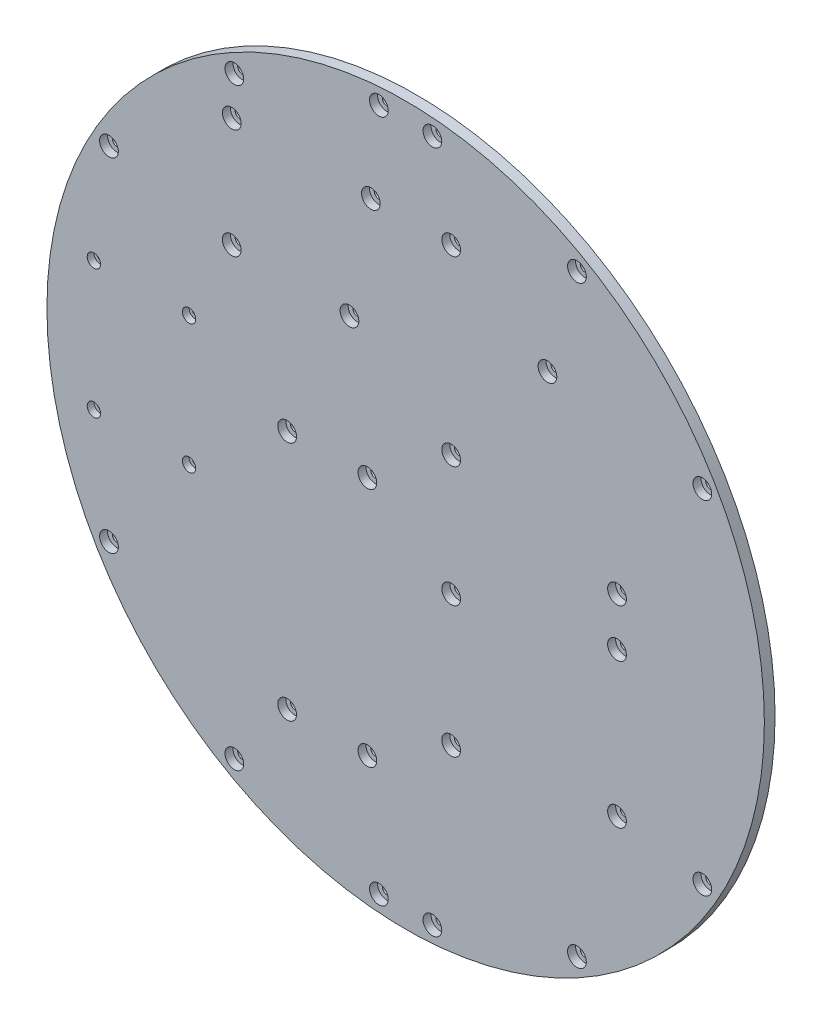
SolidWorks part; units mm, degrees
ref_plane "Plan de face" through (0, 0, 0) normal (0, 0, 1) x (1, 0, 0)
ref_plane "Plan de dessus" through (0, 0, 0) normal (0, 1, 0) x (1, 0, 0)
ref_plane "Plan de droite" through (0, 0, 0) normal (1, 0, 0) x (0, 0, -1)
sketch "Esquisse1" plane through (0, 0, 0) normal (0, 0, 1) x (1, 0, 0)
  line L0 (0, 0) -> (0, -128.06) construction
  line L1 (10, -127.669) -> (-10, -127.669) construction
  line L2 (0, 0) -> (0, 128.06) construction
  line L3 (10, 127.669) -> (-10, 127.669) construction
  line L4 (-64.03, -110.9032) -> (64.03, 110.9032) construction
  line L5 (110.9032, 64.03) -> (-110.9032, -64.03) construction
  line L6 (-64.03, 110.9032) -> (64.03, -110.9032) construction
  line L7 (-110.9032, 64.03) -> (110.9032, -64.03) construction
  circle A0 centre (0, 0) radius 134.09
  circle A1 centre (10, -127.669) radius 1.75
  circle A2 centre (-10, -127.669) radius 1.75
  circle A3 centre (0, 0) radius 128.06 construction
  circle A4 centre (10, 127.669) radius 1.75
  circle A5 centre (-10, 127.669) radius 1.75
  circle A6 centre (64.03, 110.9032) radius 1.75
  circle A7 centre (110.9032, 64.03) radius 1.75
  circle A8 centre (110.9032, -64.03) radius 1.75
  circle A9 centre (64.03, -110.9032) radius 1.75
  circle A10 centre (-64.03, -110.9032) radius 1.75
  circle A11 centre (-110.9032, -64.03) radius 1.75
  circle A12 centre (-110.9032, 64.03) radius 1.75
  circle A13 centre (-64.03, 110.9032) radius 1.75
  point P7 (0, -127.669)
  point P14 (0, 127.669)
  point P17 (0, 0)
  point P18 (0, 0)
  point P23 (0, 0)
  point P26 (0, 0)
  dimension "D1" = 256.12
  dimension "D3" = 3.5
  dimension "D8" = 268.18
  dimension "D2" = 20
  dimension "D4" = 30
  dimension "D5" = 30
  dimension "D6" = 30
  dimension "D7" = 30
extrude "Boss.-Extru.1" add sketch "Esquisse1" along normal blind 4
sketch "Esquisse2" plane through (0, 0, 4) normal (0, 0, 1) x (1, 0, 0)
  circle A0 centre (64.03, -110.9032) radius 3.5
  circle A1 centre (110.9032, -64.03) radius 3.5
  circle A2 centre (110.9032, 64.03) radius 3.5
  circle A3 centre (64.03, 110.9032) radius 3.5
  circle A4 centre (10, 127.669) radius 3.5
  circle A5 centre (-10, 127.669) radius 3.5
  circle A6 centre (-64.03, 110.9032) radius 3.5
  circle A7 centre (-110.9032, 64.03) radius 3.5
  circle A8 centre (-110.9032, -64.03) radius 3.5
  circle A9 centre (-64.03, -110.9032) radius 3.5
  circle A10 centre (-10, -127.669) radius 3.5
  circle A11 centre (10, -127.669) radius 3.5
  dimension "D1" = 7
extrude "Enlèv. mat.-Extru.1" cut sketch "Esquisse2" against normal blind 3
sketch "Esquisse3" plane through (0, 0, 4) normal (0, 0, 1) x (1, 0, 0)
  line L0 (-116.5279, -24.13) -> (-116.5279, 24.13) construction
  line L1 (-116.5279, 24.13) -> (-80.9679, 24.13) construction
  line L2 (-80.9679, 24.13) -> (-80.9679, -24.13) construction
  line L3 (-80.9679, -24.13) -> (-116.5279, -24.13) construction
  circle A0 centre (0, 0) radius 119 construction
  circle A3 centre (-116.5279, -24.13) radius 1.25
  circle A4 centre (-116.5279, 24.13) radius 1.25
  circle A5 centre (-80.9679, 24.13) radius 1.25
  circle A6 centre (-80.9679, -24.13) radius 1.25
  dimension "D1" = 238
  dimension "D2" = 35.56
  dimension "D4" = 2.5
  dimension "D3" = 48.26
extrude "Enlèv. mat.-Extru.2" cut sketch "Esquisse3" against normal up to next
sketch "Esquisse4" plane through (0, 0, 4) normal (0, 0, 1) x (1, 0, 0)
  circle A0 centre (-116.5279, -24.13) radius 2.5
  circle A1 centre (-116.5279, 24.13) radius 2.5
  circle A2 centre (-80.9679, 24.13) radius 2.5
  circle A3 centre (-80.9679, -24.13) radius 2.5
  dimension "D1" = 5
extrude "Enlèv. mat.-Extru.3" cut sketch "Esquisse4" against normal blind 2.5
sketch "Esquisse5" plane through (0, 0, 4) normal (0, 0, 1) x (1, 0, 0)
  circle A0 centre (-44.3, -85) radius 1.75
  circle A1 centre (-44.3, 5) radius 1.75
  circle A2 centre (-14.3, 5) radius 1.75
  circle A3 centre (-14.3, -85) radius 1.75
  circle A5 centre (0, 0) radius 134.09
  circle A6 centre (0, 0) radius 134.09 construction
  dimension "D4" = 3.5
  dimension "D1" = 90
  dimension "D2" = 30
  dimension "D3" = 5
  dimension "D6" = 14.3
  dimension "D5" = 0
extrude "Enlèv. mat.-Extru.4" cut sketch "Esquisse5" against normal up to next
sketch "Esquisse6" plane through (0, 0, 4) normal (0, 0, 1) x (1, 0, 0)
  circle A0 centre (-44.3, -85) radius 3.5
  circle A1 centre (-14.3, -85) radius 3.5
  circle A2 centre (-44.3, 5) radius 3.5
  circle A3 centre (-14.3, 5) radius 3.5
  dimension "D1" = 7
extrude "Enlèv. mat.-Extru.5" cut sketch "Esquisse6" against normal blind 3
sketch "Esquisse7" plane through (0, 0, 4) normal (0, 0, 1) x (1, 0, 0)
  circle A0 centre (-65, 55) radius 1.75
  circle A1 centre (-65, 96) radius 1.75
  circle A2 centre (-21, 54) radius 1.75
  circle A3 centre (-13, 96) radius 1.75
  circle A4 centre (-44.3, 5) radius 3.5 construction
  circle A6 centre (-14.3, 5) radius 3.5 construction
  dimension "D5" = 3.5
  dimension "D7" = 6.7
  dimension "D1" = 44
  dimension "D2" = 41
  dimension "D3" = 42
  dimension "D4" = 52
  dimension "D6" = 50
extrude "Enlèv. mat.-Extru.6" cut sketch "Esquisse7" against normal up to next
sketch "Esquisse8" plane through (0, 0, 4) normal (0, 0, 1) x (1, 0, 0)
  circle A0 centre (-65, 55) radius 3.5
  circle A1 centre (-65, 96) radius 3.5
  circle A2 centre (-21, 54) radius 3.5
  circle A3 centre (-13, 96) radius 3.5
  dimension "D1" = 7
extrude "Enlèv. mat.-Extru.7" cut sketch "Esquisse8" against normal blind 3
sketch "Esquisse9" plane through (0, 0, 0) normal (0, 0, -1) x (-1, 0, 0)
  circle A0 centre (-17, 96) radius 1.75
  circle A1 centre (-17, 28) radius 1.75
  circle A2 centre (-53, 73) radius 1.75
  circle A3 centre (-79, 14) radius 1.75
  circle A4 centre (13, 96) radius 1.75 construction
  circle A5 centre (13, 96) radius 1.75 construction
  dimension "D1" = 3.5
  dimension "D2" = 68
  dimension "D3" = 23
  dimension "D4" = 36
  dimension "D5" = 62
  dimension "D6" = 30
  dimension "D7" = 82
extrude "Enlèv. mat.-Extru.8" cut sketch "Esquisse9" against normal up to next
sketch "Esquisse10" plane through (0, 0, 4) normal (0, 0, 1) x (1, 0, 0)
  circle A0 centre (17, 28) radius 3.5
  circle A1 centre (17, 96) radius 3.5
  circle A2 centre (53, 73) radius 3.5
  circle A3 centre (79, 14) radius 3.5
  dimension "D1" = 7
extrude "Enlèv. mat.-Extru.9" cut sketch "Esquisse10" against normal blind 3
sketch "Esquisse11" plane through (0, 0, 0) normal (0, 0, -1) x (-1, 0, 0)
  circle A0 centre (-17, -17) radius 1.75
  circle A1 centre (-17, -66) radius 1.75
  circle A2 centre (-79, -4) radius 1.75
  circle A3 centre (-79, -58) radius 1.75
  circle A4 centre (-17, 28) radius 1.75 construction
  circle A5 centre (-17, 28) radius 1.75 construction
  circle A6 centre (-79, 14) radius 1.75 construction
  point P11 (0, 0)
  point P12 (0, 0)
  point P13 (0, 0)
  point P14 (-79, -30.1179)
  point P15 (-79, -10.2523)
  dimension "D1" = 3.5
  dimension "D2" = 49
  dimension "D6" = 18
  dimension "D3" = 62
  dimension "D4" = 13
  dimension "D5" = 54
extrude "Enlèv. mat.-Extru.10" cut sketch "Esquisse11" against normal up to next
sketch "Esquisse12" plane through (0, 0, 4) normal (0, 0, 1) x (1, 0, 0)
  circle A0 centre (17, -66) radius 3.5
  circle A1 centre (17, -17) radius 3.5
  circle A2 centre (79, -4) radius 3.5
  circle A3 centre (79, -58) radius 3.5
  dimension "D1" = 7
extrude "Enlèv. mat.-Extru.11" cut sketch "Esquisse12" against normal blind 3
